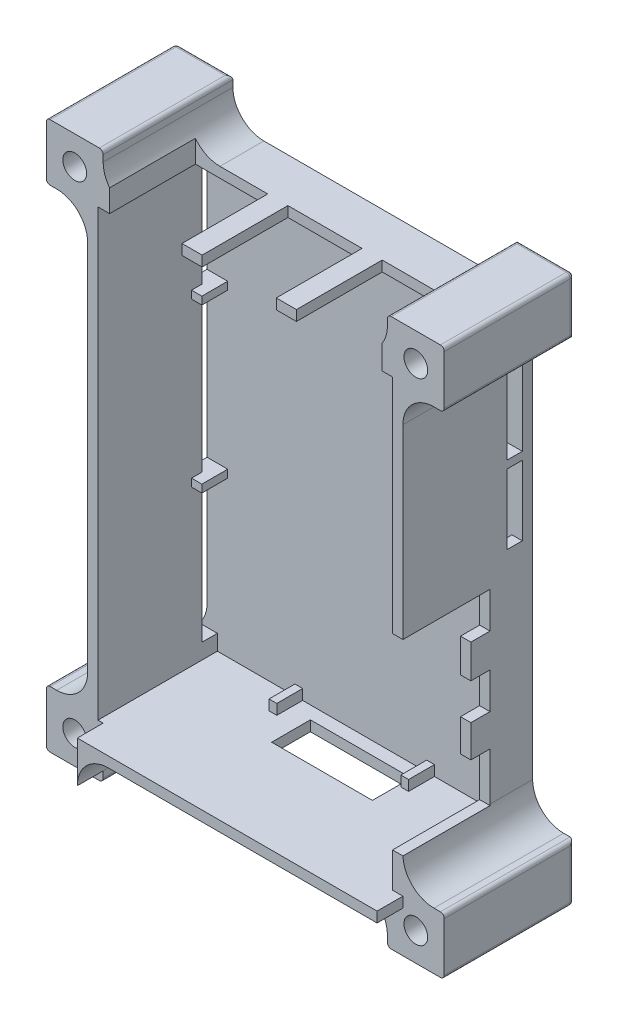
SolidWorks part; units mm, degrees
ref_plane "Front Plane" through (0, 0, 0) normal (0, 0, 1) x (1, 0, 0)
ref_plane "Top Plane" through (0, 0, 0) normal (0, 1, 0) x (1, 0, 0)
ref_plane "Right Plane" through (0, 0, 0) normal (1, 0, 0) x (0, 0, -1)
sketch "Sketch1" plane through (0, 0, 0) normal (0, 0, 1) x (1, 0, 0)
  line L1 (0, 0) -> (61, 0)
  line L2 (0, 0) -> (0, 90)
  line L3 (0, 90) -> (61, 90)
  line L4 (61, 0) -> (61, 90)
  dimension "D1" = 61
  dimension "D2" = 90
extrude "Boss-Extrude1" add sketch "Sketch1" along normal blind 2
sketch "Sketch2" plane through (0, 0, 2) normal (0, 0, 1) x (1, 0, 0)
  line L7 (0, -16.225) -> (0, 16.225) construction
  line L8 (0, 90) -> (0, 0)
  line L9 (2, 90) -> (2, 2)
  line L10 (2, 2) -> (59, 2)
  line L11 (59, 2) -> (59, 90)
  line L12 (2, 88) -> (2, 2)
  line L13 (2, 2) -> (59, 2)
  line L14 (59, 2) -> (59, 88)
  line L15 (0, 0) -> (61, 0)
  line L18 (61, 90) -> (61, 0)
  line L20 (2, 88) -> (59, 88)
  line L21 (0, 90) -> (61, 90)
  dimension "D1" = 2
extrude "Boss-Extrude2" add sketch "Sketch2" along normal blind 6.6
sketch "Sketch3" plane through (0, 0, 2) normal (0, 0, 1) x (1, 0, 0)
  line L0 (59, 2) -> (2, 2) construction
  line L1 (44, 2) -> (42.5, 2)
  line L2 (44, 2) -> (44, 4)
  line L3 (44, 4) -> (42.5, 4)
  line L4 (42.5, 2) -> (42.5, 4)
  line L5 (2, 2) -> (2, 88) construction
  line L6 (17, 2) -> (18.5, 2)
  line L7 (17, 2) -> (17, 4)
  line L8 (17, 4) -> (18.5, 4)
  line L9 (18.5, 2) -> (18.5, 4)
  line L10 (2, 32) -> (4, 32)
  line L11 (2, 32) -> (2, 33.5)
  line L12 (2, 33.5) -> (4, 33.5)
  line L13 (4, 32) -> (4, 33.5)
  line L14 (59, 88) -> (59, 2) construction
  line L15 (59, 32) -> (57, 32)
  line L16 (59, 32) -> (59, 33.5)
  line L17 (59, 33.5) -> (57, 33.5)
  line L18 (57, 32) -> (57, 33.5)
  line L19 (2, 2) -> (2, 88) construction
  line L20 (59, 63.5) -> (57, 63.5)
  line L21 (59, 63.5) -> (59, 65)
  line L22 (59, 65) -> (57, 65)
  line L23 (57, 63.5) -> (57, 65)
  line L24 (2, 63.5) -> (4, 63.5)
  line L25 (2, 63.5) -> (2, 65)
  line L26 (2, 65) -> (4, 65)
  line L27 (4, 63.5) -> (4, 65)
  line L28 (59, 2) -> (2, 2) construction
  dimension "D1" = 1.5
  dimension "D2" = 1.5
  dimension "D3" = 1.5
  dimension "D4" = 1.5
  dimension "D5" = 1.5
  dimension "D6" = 1.5
  dimension "D7" = 2
  dimension "D8" = 2
  dimension "D9" = 2
  dimension "D10" = 2
  dimension "D11" = 2
  dimension "D12" = 2
  dimension "D13" = 30
  dimension "D14" = 30
  dimension "D15" = 30
  dimension "D16" = 30
  dimension "D17" = 15
  dimension "D18" = 15
extrude "Boss-Extrude3" add sketch "Sketch3" along normal blind 5
sketch "Sketch4" plane through (0, 0, 8.6) normal (0, 0, 1) x (1, 0, 0)
  line L1 (61, 90) -> (0, 90)
  line L3 (59, 88) -> (2, 88)
  line L5 (61, 90) -> (61, 0)
  line L6 (0, 90) -> (0, 0)
  line L7 (0, 0) -> (61, 0)
  line L8 (2, 2) -> (59, 2)
  line L9 (2, 88) -> (2, 2)
  line L10 (59, 2) -> (59, 88)
  line L11 (59, 2) -> (59, 88) construction
extrude "Boss-Extrude4" add sketch "Sketch4" along normal blind 16.5
sketch "Sketch5" plane through (0, 90, 0) normal (0, 1, 0) x (1, 0, 0)
  line L1 (57, -8.5) -> (40.4, -8.5)
  line L3 (57, -22.25) -> (40.4, -22.25) construction
  line L4 (40.4, -8.5) -> (40.4, -22.25)
  line L5 (61, 0) -> (0, 0) construction
  line L6 (61, -25.1) -> (0, -25.1) construction
  line L7 (36.5, -25.1) -> (22.15, -25.1)
  line L8 (36.5, -25.1) -> (36.5, -8.5)
  line L9 (36.5, -8.5) -> (22.15, -8.5)
  line L10 (22.15, -25.1) -> (22.15, -8.5)
  line L11 (0, -25.1) -> (0, 0) construction
  line L12 (18.25, -25.1) -> (4.25, -25.1)
  line L13 (18.25, -25.1) -> (18.25, -8.5)
  line L14 (18.25, -8.5) -> (4.25, -8.5)
  line L15 (4.25, -25.1) -> (4.25, -8.5)
  line L17 (57, -25.1) -> (40.4, -25.1)
  line L19 (57, -22.25) -> (40.4, -22.25) construction
  line L20 (40.4, -25.1) -> (40.4, -22.25)
  line L21 (57, -8.5) -> (57, -25.1)
  line L22 (61, -25.1) -> (61, 0) construction
  point P21 (61, -12.55)
  dimension "D2" = 16.6
  dimension "D3" = 13.75
  dimension "D4" = 8.5
  dimension "D5" = 4.25
  dimension "D6" = 3.9
  dimension "D7" = 14
  dimension "D8" = 8.5
  dimension "D9" = 8.5
  dimension "D10" = 3.9
  dimension "D11" = 4
  dimension "D12" = 0
extrude "Cut-Extrude1" cut sketch "Sketch5" against normal blind 2
sketch "Sketch7" plane through (61, 0, 0) normal (1, 0, 0) x (0, 0, -1)
  line L0 (-11.95, 18.25) -> (-11.95, 24.5)
  line L8 (-11.95, 18.25) -> (-8.25, 18.25)
  line L9 (-8.25, 8.75) -> (-8.25, 18.25)
  line L10 (-11.95, 24.5) -> (-8.25, 24.5)
  line L12 (-11.95, 38) -> (-8.25, 38)
  line L14 (-11.95, 31.5) -> (-8.25, 31.5)
  line L18 (-25.1, 0) -> (-25.1, 90) construction
  line L19 (-25.1, 8.75) -> (-25.1, 45)
  line L21 (-11.95, 38) -> (-11.95, 31.5)
  line L22 (-8.25, 8.75) -> (-25.1, 8.75)
  line L23 (-25.1, 45) -> (-8.25, 45)
  line L24 (-25.1, 0) -> (0, 0) construction
  line L25 (-8.25, 24.5) -> (-8.25, 31.5)
  line L26 (-8.25, 38) -> (-8.25, 45)
  line L28 (0, 0) -> (0, 90) construction
  line L29 (0, 33.55) -> (0, -33.55) construction
  line L30 (-2, 85) -> (-5, 85)
  line L31 (-2, 85) -> (-2, 50)
  line L32 (-2, 50) -> (-5, 50)
  line L33 (-5, 85) -> (-5, 50)
  line L34 (-25.1, 90) -> (0, 90) construction
  point P0 (-8.25, 13.5)
  point P16 (-8.25, 41.5)
  point P18 (-10.1, 18.25)
  point P20 (-8.25, 28)
  dimension "D1" = 9.5
  dimension "D2" = 28
  dimension "D3" = 7
  dimension "D4" = 7
  dimension "D5" = 13.5
  dimension "D6" = 41.5
  dimension "D7" = 3.7
  dimension "D8" = 3.7
  dimension "D9" = 8.25
  dimension "D10" = 0
  dimension "D11" = 0
  dimension "D12" = 2
  dimension "D13" = 5
  dimension "D14" = 3
  dimension "D15" = 35
extrude "Cut-Extrude2" cut sketch "Sketch7" against normal blind 2
sketch "Sketch8" plane through (0, 0, 0) normal (0, -1, 0) x (-1, 0, 0)
  line L2 (-22.5, -12) -> (-22.5, -4.5)
  line L3 (-22.5, -4.5) -> (-42, -4.5)
  line L4 (-42, -12) -> (-42, -4.5)
  line L5 (0, 16.555) -> (0, -16.555) construction
  line L6 (-61, -25.1) -> (-61, 0) construction
  line L7 (-33.55, 0) -> (33.55, 0) construction
  line L8 (-22.5, -12) -> (-42, -12)
  dimension "D1" = 22.5
  dimension "D2" = 19
  dimension "D3" = 4.5
  dimension "D4" = 7.5
extrude "Cut-Extrude3" cut sketch "Sketch8" against normal blind 2
sketch "Sketch9" plane through (0, 0, 0) normal (-1, 0, 0) x (0, 0, 1)
  line L0 (0, -33.55) -> (0, 33.55) construction
  line L1 (5, 85) -> (2, 85)
  line L2 (5, 85) -> (5, 5)
  line L3 (5, 5) -> (2, 5)
  line L4 (2, 85) -> (2, 5)
  line L5 (25.1, 90) -> (0, 90) construction
  line L6 (16.555, 0) -> (-16.555, 0) construction
  dimension "D1" = 2
  dimension "D2" = 3
  dimension "D3" = 5
  dimension "D4" = 5
extrude "Cut-Extrude4" cut sketch "Sketch9" against normal blind 2
sketch "Sketch10" plane through (0, 0, 25.1) normal (0, 0, 1) x (1, 0, 0)
  line L0 (61, 0) -> (61, 8.75) construction
  line L1 (0, 0) -> (61, 0)
  line L2 (0, 0) -> (0, 2)
  line L3 (0, 2) -> (61, 2)
  line L4 (61, 0) -> (61, 2)
  dimension "D1" = 2
extrude "Boss-Extrude5" add sketch "Sketch10" along normal blind 5
sketch "Sketch12" plane through (2, 0, 0) normal (-1, 0, 0) x (0, 0, 1)
  line L0 (5, 63.5) -> (2, 63.5) construction
  line L1 (2, 65) -> (5, 65)
  line L2 (2, 65) -> (2, 63.5)
  line L3 (2, 63.5) -> (5, 63.5)
  line L4 (5, 65) -> (5, 63.5)
  line L5 (5, 32) -> (2, 32) construction
  line L6 (2, 33.5) -> (5, 33.5)
  line L7 (2, 33.5) -> (2, 32)
  line L8 (2, 32) -> (5, 32)
  line L9 (5, 33.5) -> (5, 32)
extrude "Boss-Extrude6" add sketch "Sketch12" along normal blind 2
sketch "Sketch13" plane through (59, 0, 0) normal (1, 0, 0) x (0, 0, -1)
  line L1 (-2, 63.5) -> (-5, 63.5)
  line L2 (-2, 63.5) -> (-2, 65)
  line L3 (-2, 65) -> (-5, 65)
  line L4 (-5, 63.5) -> (-5, 65)
extrude "Boss-Extrude7" add sketch "Sketch13" along normal blind 2
sketch "Sketch20" plane through (0, 0, 0) normal (0, 0, -1) x (-1, 0, 0)
  line L0 (-61, 90) -> (0, 90) construction
  line L1 (-3, 3) -> (8, 3)
  line L2 (-3, 3) -> (-3, -8)
  line L3 (-3, -8) -> (8, -8)
  line L4 (8, 3) -> (8, -8)
  line L5 (-3, 3) -> (8, -8) construction
  line L6 (-3, -8) -> (8, 3) construction
  line L7 (-58, 87) -> (-69, 87)
  line L8 (-58, 87) -> (-58, 98)
  line L9 (-58, 98) -> (-69, 98)
  line L10 (-69, 87) -> (-69, 98)
  line L11 (-58, 87) -> (-69, 98) construction
  line L12 (-58, 98) -> (-69, 87) construction
  line L13 (-61, 0) -> (-61, 90) construction
  line L14 (0, 0) -> (-61, 0) construction
  line L15 (0, 90) -> (0, 0) construction
  point P4 (2.5, -2.5)
  point P9 (-63.5, 92.5)
  dimension "D1" = 3
  dimension "D2" = 3
  dimension "D3" = 11
  dimension "D4" = 11
  dimension "D5" = 3
  dimension "D6" = 11
  dimension "D7" = 3
  dimension "D8" = 11
extrude "Boss-Extrude8" add sketch "Sketch20" against normal up to surface (25.1 mm away) up to face at (2.0833, 60, 25.1)
sketch "Sketch25" plane through (0, 0, 25.1) normal (0, 0, 1) x (1, 0, 0)
  line L1 (3, 3) -> (-8, 3)
  line L2 (3, 3) -> (3, -8)
  line L3 (3, -8) -> (-8, -8)
  line L4 (-8, 3) -> (-8, -8)
  line L5 (3, 3) -> (-8, -8) construction
  line L6 (3, -8) -> (-8, 3) construction
  line L7 (3, -8) -> (3.25, -8)
  line L8 (3, -8) -> (3, 3)
  line L9 (3, 3) -> (3.25, 3)
  line L10 (3.25, -8) -> (3.25, 3)
  line L11 (3, -8) -> (3.25, 3) construction
  line L12 (3, 3) -> (3.25, -8) construction
  point P4 (-2.5, -2.5)
  point P10 (3.125, -2.5)
  dimension "D1" = 0.25
extrude "Cut-Extrude11" cut sketch "Sketch25" along normal through all contours L2 L1 L4 L3 | L8 L7 L10 L9
sketch "Sketch26" plane through (0, 0, 25.1) normal (0, 0, 1) x (1, 0, 0)
  line L1 (3, 3) -> (2, 3)
  line L2 (3, 3) -> (3, 2)
  line L3 (3, 2) -> (2, 2)
  line L4 (2, 3) -> (2, 2)
  line L5 (3, 3) -> (2, 2) construction
  line L6 (3, 2) -> (2, 3) construction
  line L7 (58, 87) -> (59, 87)
  line L8 (58, 87) -> (58, 88)
  line L9 (58, 88) -> (59, 88)
  line L10 (59, 87) -> (59, 88)
  line L11 (58, 87) -> (59, 88) construction
  line L12 (58, 88) -> (59, 87) construction
  point P4 (2.5, 2.5)
  point P10 (58.5, 87.5)
  dimension "D1" = 1
  dimension "D2" = 1
  dimension "D3" = 1
  dimension "D4" = 1
extrude "Cut-Extrude12" cut sketch "Sketch26" against normal up to surface (23.1 mm away) up to face at (30.4, 40.25, 2)
sketch "Sketch27" plane through (0, 0, 25.1) normal (0, 0, 1) x (1, 0, 0)
  line L0 (63.5, 98) -> (63.5, 87) construction
  line L1 (58, 98) -> (69, 98) construction
  line L2 (69, 87) -> (61, 87) construction
  line L3 (69, 92.5) -> (58, 92.5) construction
  line L4 (69, 98) -> (69, 87) construction
  line L5 (58, 90) -> (58, 98) construction
  line L6 (-2.5, -8) -> (-2.5, 3) construction
  line L7 (3, -8) -> (-8, -8) construction
  line L8 (-8, 3) -> (0, 3) construction
  line L9 (-8, -2.5) -> (3, -2.5) construction
  line L10 (-8, -8) -> (-8, 3) construction
  line L11 (3, 0) -> (3, -8) construction
  circle A0 centre (-2.5, -2.5) radius 2.3
  circle A1 centre (63.5, 92.5) radius 2.3
  dimension "D1" = 4.6
  dimension "D2" = 4.6
extrude "Cut-Extrude13" cut sketch "Sketch27" against normal through all
sketch "Sketch31" plane through (0, 0, 0) normal (0, 0, -1) x (-1, 0, 0)
  line L0 (-69, 98) -> (-69, 87) construction
  line L1 (-60.8731, 87.95) -> (-58.2461, 92.5)
  line L2 (-58.2461, 92.5) -> (-60.8731, 97.05)
  line L3 (-60.8731, 97.05) -> (-66.1269, 97.05)
  line L4 (-66.1269, 97.05) -> (-68.7539, 92.5)
  line L5 (-68.7539, 92.5) -> (-66.1269, 87.95)
  line L6 (-66.1269, 87.95) -> (-60.8731, 87.95)
  line L7 (4.775, -6.4404) -> (7.05, -2.5)
  line L8 (7.05, -2.5) -> (4.775, 1.4404)
  line L9 (4.775, 1.4404) -> (0.225, 1.4404)
  line L10 (0.225, 1.4404) -> (-2.05, -2.5)
  line L11 (-2.05, -2.5) -> (0.225, -6.4404)
  line L12 (0.225, -6.4404) -> (4.775, -6.4404)
  line L13 (8, -8) -> (8, 3) construction
  circle A0 centre (-63.5, 92.5) radius 4.55 construction
  circle A1 centre (2.5, -2.5) radius 3.9404 construction
  dimension "D1" = 9.1
  dimension "D2" = 9.1
  dimension "D3" = 30
  dimension "D4" = 30
extrude "Cut-Extrude17" cut sketch "Sketch31" against normal blind 6
fillet "Fillet3" radius 6 1 edges at (58, 90, 12.55) type face fillet first side face at (29.5687, 90, 15.7375) second side face at (58, 94, 12.55)
fillet "Fillet4" radius 6 1 edges at (61, 87, 12.55) type face fillet first side face at (61, 75, 3.5) second side face at (65, 87, 12.55)
sketch "Sketch33" plane through (0, 0, 25.1) normal (0, 0, 1) x (1, 0, 0)
  line L0 (2, 2) -> (3.25, 2) construction
  line L1 (3.25, 0) -> (3, 0)
  line L2 (3.25, 0) -> (3.25, 2)
  line L3 (3.25, 2) -> (3, 2)
  line L4 (3, 0) -> (3, 2)
  line L5 (3.25, 0) -> (3, 2) construction
  line L6 (3.25, 2) -> (3, 0) construction
  point P4 (3.125, 1)
  dimension "D1" = 0.25
extrude "Boss-Extrude10" add sketch "Sketch33" along normal up to surface (5 mm away) up to face at (32.125, 1, 30.1)
fillet "Fillet7" radius 6 1 edges at (3, 0, 12.55) type face fillet first side face at (3, -4, 12.55) second side face at (32.25, 0, 8.25)
fillet "Fillet8" radius 6 1 edges at (0, 3, 12.55) type face fillet first side face at (-4, 3, 12.55) second side face at (0, 48.5, 3.5)
sketch "Sketch34" plane through (0, 0, 25.1) normal (0, 0, 1) x (1, 0, 0)
  line L0 (18.25, 90) -> (4.25, 90) construction
  line L1 (59, 3) -> (69, 3)
  line L2 (58, 2) -> (58, -8)
  line L3 (58, -8) -> (69, -8)
  line L4 (69, 3) -> (69, -8)
  line L5 (59, 2) -> (69, -8) construction
  line L6 (58, -8) -> (69, 3) construction
  line L7 (2, 87) -> (-8, 87)
  line L8 (3, 88) -> (3, 98)
  line L9 (3, 98) -> (-8, 98)
  line L10 (-8, 87) -> (-8, 98)
  line L11 (2, 88) -> (-8, 98) construction
  line L12 (3, 98) -> (-8, 87) construction
  line L13 (0, 90) -> (0, 9) construction
  line L14 (61, 0) -> (61, 2) construction
  line L15 (9, 0) -> (61, 0) construction
  line L16 (59, 88) -> (2, 88) construction
  line L17 (2, 88) -> (2, 2) construction
  line L18 (3, 88) -> (2, 88)
  line L19 (2, 88) -> (2, 87)
  line L20 (59, 2) -> (59, 8.75) construction
  line L21 (44, 2) -> (59, 2) construction
  line L22 (59, 2) -> (59, 3)
  line L23 (58, 2) -> (59, 2)
  point P4 (63.5, -2.5)
  point P9 (-2.5, 92.5)
  dimension "D1" = 3
  dimension "D2" = 3
  dimension "D3" = 3
  dimension "D4" = 3
  dimension "D5" = 11
  dimension "D6" = 11
  dimension "D7" = 11
  dimension "D8" = 11
extrude "Boss-Extrude11" add sketch "Sketch34" against normal up to surface (25.1 mm away) up to face at (30.5, 45, 0)
sketch "Sketch35" plane through (0, 0, 25.1) normal (0, 0, 1) x (1, 0, 0)
  line L0 (-2.5, 98) -> (-2.5, 87) construction
  line L1 (3, 98) -> (-8, 98) construction
  line L2 (-8, 87) -> (0, 87) construction
  line L3 (-8, 92.5) -> (3, 92.5) construction
  line L4 (-8, 98) -> (-8, 87) construction
  line L5 (3, 90) -> (3, 98) construction
  line L6 (63.5, -8) -> (63.5, 3) construction
  line L7 (58, -8) -> (69, -8) construction
  line L8 (69, 3) -> (61, 3) construction
  line L9 (69, -2.5) -> (58, -2.5) construction
  line L10 (69, -8) -> (69, 3) construction
  line L11 (58, 0) -> (58, -8) construction
  circle A0 centre (-2.5, 92.5) radius 2.3
  circle A1 centre (63.5, -2.5) radius 2.3
  point P28 (-2.5, 92.5)
  dimension "D1" = 4.6
  dimension "D2" = 4.6
extrude "Cut-Extrude18" cut sketch "Sketch35" against normal through all
fillet "Fillet9" radius 6 1 edges at (0, 87, 12.55) type face fillet first side face at (-4, 87, 12.55) second side face at (0, 48.5, 3.5)
fillet "Fillet10" radius 6 1 edges at (3, 90, 12.55) type face fillet first side face at (3, 94, 12.55) second side face at (25.2214, 90, 14.4)
fillet "Fillet11" radius 6 1 edges at (61, 3, 12.55) type face fillet first side face at (65, 3, 12.55) second side face at (61, 39.6, 10.585)
fillet "Fillet12" radius 6 1 edges at (58, 0, 12.55) type face fillet first side face at (58, -4, 12.55) second side face at (32.25, 0, 8.25)
fillet "Fillet13" radius 0.75 20 edges at (69, -2.5, 0) (63.5, -8, 0) (-2.5, -8, 0) (-8, -2.5, 0) (-8, 92.5, 0) (-2.5, 98, 0) (69, 92.5, 0) (63.5, 98, 0) (69, 87, 12.55) (69, 98, 12.55) (58, 98, 12.55) (3, 98, 12.55) (-8, 98, 12.55) (-8, 87, 12.55) (-8, 3, 12.55) (-8, -8, 12.55) (3, -8, 12.55) (69, 3, 12.55) (58, -8, 12.55) (69, -8, 12.55)
sketch "Sketch36" plane through (0, 0, 0) normal (0, 0, -1) x (-1, 0, 0)
  line L0 (8, 97.25) -> (8, 87.75) construction
  line L1 (-58.95, -2.5) -> (-61.225, 1.4404)
  line L2 (-61.225, 1.4404) -> (-65.775, 1.4404)
  line L3 (-65.775, 1.4404) -> (-68.05, -2.5)
  line L4 (-68.05, -2.5) -> (-65.775, -6.4404)
  line L5 (-65.775, -6.4404) -> (-61.225, -6.4404)
  line L6 (-61.225, -6.4404) -> (-58.95, -2.5)
  line L7 (-2.05, 92.5) -> (0.225, 88.5596)
  line L8 (0.225, 88.5596) -> (4.775, 88.5596)
  line L9 (4.775, 88.5596) -> (7.05, 92.5)
  line L10 (7.05, 92.5) -> (4.775, 96.4404)
  line L11 (4.775, 96.4404) -> (0.225, 96.4404)
  line L12 (0.225, 96.4404) -> (-2.05, 92.5)
  line L13 (-69, -7.25) -> (-69, 2.25) construction
  circle A0 centre (-63.5, -2.5) radius 3.9404 construction
  circle A1 centre (2.5, 92.5) radius 3.9404 construction
  dimension "D1" = 30
  dimension "D2" = 30
  dimension "D3" = 9.1
  dimension "D4" = 9.1
extrude "Cut-Extrude19" cut sketch "Sketch36" against normal blind 6
